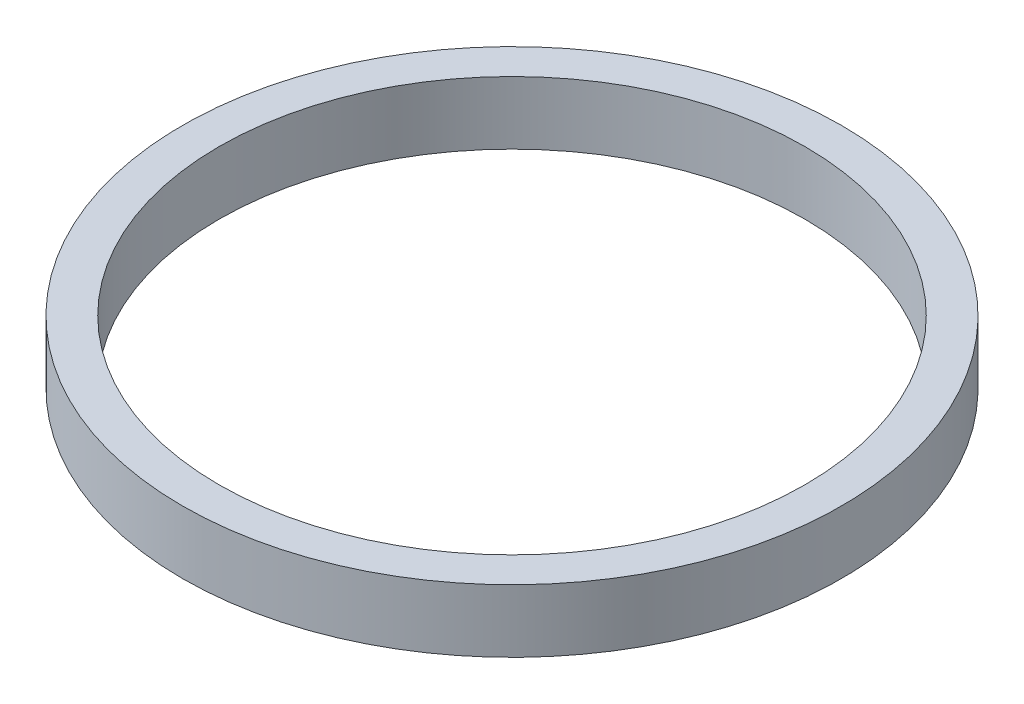
SolidWorks part; units mm, degrees
material "Hexcel AS4C (3000 Filaments)"
ref_plane "Front Plane" through (0, 0, 0) normal (0, 0, 1) x (1, 0, 0)
ref_plane "Top Plane" through (0, 0, 0) normal (0, 1, 0) x (1, 0, 0)
ref_plane "Right Plane" through (0, 0, 0) normal (1, 0, 0) x (0, 0, -1)
sketch "Sketch1" plane through (0, 0, 0) normal (0, 0, 1) x (1, 0, 0)
  line L0 (-60, 13.67) -> (-60, 0.785) construction
  line L1 (-67.5, 13.67) -> (-67.5, 0.785) construction
  line L2 (-60, 13.67) -> (-60, 0.785)
  line L3 (-67.5, 13.67) -> (-67.5, 0.785)
  line L4 (-60, 13.67) -> (-67.5, 13.67)
  line L5 (-60, 0.785) -> (-67.5, 0.785)
  line L6 (0, -200069.0475) -> (0, 200086.9028) construction
  line L7 (0, -200069.0475) -> (0, 200086.9028) construction
revolve "Revolve1" add sketch "Sketch1" angle 360 about L7
